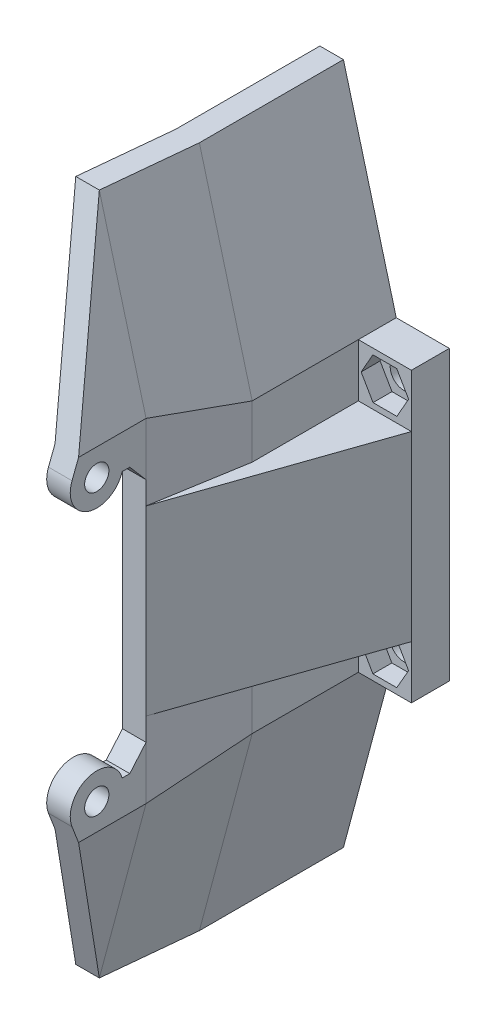
SolidWorks part; units mm, degrees
note: The reader was unsure of these and kept them because the rebuilt part matched: shared geometry of "Esquisse3<4>".
ref_plane "Plan de face" through (0, 0, 0) normal (0, 0, 1) x (1, 0, 0)
ref_plane "Plan de dessus" through (0, 0, 0) normal (0, 1, 0) x (1, 0, 0)
ref_plane "Plan de droite" through (0, 0, 0) normal (1, 0, 0) x (0, 0, -1)
sketch "Esquisse1" plane through (0, 0, 0) normal (0, 0, 1) x (1, 0, 0)
  line L1 (-10.1058, -19) -> (-10.1058, 19)
  line L2 (-10.1058, 19) -> (-17.0725, 45)
  line L3 (-17.0725, 45) -> (-13.9667, 45)
  line L4 (-13.9667, 45) -> (-7, 19)
  line L5 (-7, -19) -> (-13.9667, -45)
  line L6 (-7, 19) -> (0, 19)
  line L7 (0, 19) -> (0, -19)
  line L8 (-7, -19) -> (0, -19)
  line L11 (-17.0725, -45) -> (-13.9667, -45)
  line L12 (-10.1058, -19) -> (-17.0725, -45)
  point P10 (0, 0)
  dimension "D1" = 3
  dimension "D2" = 3
  dimension "D3" = 165
  dimension "D4" = 7
  dimension "D5" = 38
  dimension "D6" = 165
  dimension "D7" = 90
extrude "Boss.-Extru.1" add sketch "Esquisse1" along normal blind 5
sketch "Esquisse2" plane through (0, 0, 5) normal (0, 0, 1) x (1, 0, 0)
  line L8 (-17.0725, 45) -> (-10.1058, 19)
  line L9 (-17.0725, 45) -> (-10.1058, 19)
  line L10 (-10.1058, 19) -> (-10.1058, -19)
  line L11 (-10.1058, 19) -> (-10.1058, -19)
  line L12 (-7, 19) -> (-7, -19)
  line L13 (-10.1058, -19) -> (-17.0725, -45)
  line L14 (-10.1058, -19) -> (-17.0725, -45)
  line L15 (-17.0725, -45) -> (-13.9667, -45)
  line L16 (-17.0725, -45) -> (-13.9667, -45)
  line L17 (-13.9667, -45) -> (-7, -19)
  line L18 (-13.9667, -45) -> (-7, -19)
  line L19 (-7, 19) -> (-13.9667, 45)
  line L20 (-7, -19) -> (0, -19)
  line L21 (0, -19) -> (0, 19)
  line L22 (0, 19) -> (-7, 19)
  line L23 (-7, 19) -> (-13.9667, 45)
  line L30 (-13.9667, 45) -> (-17.0725, 45)
  line L31 (-13.9667, 45) -> (-17.0725, 45)
  dimension "D1" = 0
extrude "Boss.-Extru.2" add sketch "Esquisse2" along normal blind 14
ref_plane "Plan2" through (0, 0, 31) normal (0, 0, 1) x (1, 0, 0)
sketch "Esquisse3" plane through (0, 0, 31) normal (0, 0, 1) x (1, 0, 0)
  line L0 (-18.2687, 45) -> (-15.1628, 45)
  line L1 (-15.1628, 45) -> (-9, 22)
  line L3 (-9, 22) -> (-9, -22)
  line L4 (-18.2687, 45) -> (-12.1058, 22)
  line L5 (-12.1058, -22) -> (-12.1058, 22)
  line L7 (-18.2687, -45) -> (-12.1058, -22)
  line L8 (-15.1628, -45) -> (-9, -22)
  line L9 (-18.2687, -45) -> (-15.1628, -45)
  line L19 (-7, -19) -> (-7, 19) construction
  point P5 (-9, 0)
  dimension "D2" = 2
  dimension "D3" = 44
  dimension "D4" = 44
  dimension "D5" = 3
  dimension "D13" = 3
  dimension "D14" = 165
  dimension "D15" = 165
  dimension "D16" = 90
sketch "Esquisse4" plane through (0, 0, 19) normal (0, 0, 1) x (1, 0, 0)
  line L8 (-13.9667, 45) -> (-17.0725, 45)
  line L9 (-17.0725, 45) -> (-10.1058, 19)
  line L10 (-10.1058, 19) -> (-10.1058, -19)
  line L11 (-10.1058, -19) -> (-17.0725, -45)
  line L12 (-17.0725, -45) -> (-13.9667, -45)
  line L13 (-13.9667, -45) -> (-7, -19)
  line L14 (-7, -19) -> (-7, 19)
  line L15 (-13.9667, -45) -> (-7, -19)
  line L16 (-13.9667, 45) -> (-17.0725, 45)
  line L17 (-17.0725, 45) -> (-10.1058, 19)
  line L18 (-10.1058, 19) -> (-10.1058, -19)
  line L19 (-10.1058, -19) -> (-17.0725, -45)
  line L20 (-17.0725, -45) -> (-13.9667, -45)
  line L21 (-7, 19) -> (-13.9667, 45)
  line L22 (-7, -19) -> (-7, 19)
  line L23 (-7, 19) -> (-13.9667, 45)
  dimension "D1" = 0
loft "Lissage1" add profiles "Esquisse4", "Esquisse3"
sketch "Esquisse5" plane through (0, 0, 5) normal (0, 0, 1) x (1, 0, 0)
  line L1 (-3.5, 15.5) -> (-3.5, -15.5) construction
  line L2 (0, -19) -> (0, 19) construction
  line L3 (-7, 0) -> (0, 0) construction
  line L4 (-7, -19) -> (-7, 19) construction
  line L5 (0, 19) -> (-7, 19) construction
  circle A0 centre (-3.5, -15.5) radius 1.8
  circle A1 centre (-3.5, 15.5) radius 1.8
  dimension "D1" = 3.6
  dimension "D4" = 15.5
  dimension "D2" = 3.5
  dimension "D3" = 3.5
extrude "Enlèv. mat.-Extru.1" cut sketch "Esquisse5" against normal through all
sketch "Esquisse6" plane through (0, 0, 31) normal (0, 0, 1) x (1, 0, 0)
  line L0 (-18.2687, 45) -> (-12.1058, 22) construction
  line L1 (-9, 45) -> (-18.2687, 45)
  line L2 (-9, 45) -> (-9, -45)
  line L3 (-9, 22) -> (-15.1628, 45) construction
  line L4 (-18.2687, 45) -> (-12.1058, 22)
  line L5 (9.4027, 22) -> (-26.5203, 22) construction
  line L6 (11.0972, 0) -> (-26.5203, 0) construction
  line L7 (-12.1058, 22) -> (-12.1058, -22)
  line L8 (-12.1058, 22) -> (-12.1058, -22) construction
  line L9 (-18.2687, -45) -> (-12.1058, -22)
  line L10 (-9, -45) -> (-18.2687, -45)
  line L11 (-15.1628, 45) -> (-18.2687, 45) construction
  point P2 (-9, -22)
  point P8 (-9, 22)
  point P19 (-12.1058, 0)
  point P21 (-9, 0)
  dimension "D1" = 22
extrude "Boss.-Extru.3" add sketch "Esquisse6" along normal blind 15
sketch "Esquisse7" plane through (-9, 0, 0) normal (-1, 0, 0) x (0, 0, 1)
  line L0 (66.6395, 0) -> (-18.721, 0) construction
  line L1 (31, 22) -> (31, 45) construction
  line L2 (34.1459, 17.5) -> (33.1459, 17.5)
  line L3 (33.1459, 17.5) -> (31, 15)
  line L5 (31, 22) -> (31, -22) construction
  line L6 (37.5, 15) -> (27.5292, 15) construction
  line L8 (40.7642, 19.7629) -> (31, 45)
  line L10 (31, 15) -> (31, 45)
  line L11 (31, -15) -> (31, -45)
  line L12 (40.7642, -19.7629) -> (31, -45)
  line L13 (33.1459, -17.5) -> (31, -15)
  line L14 (34.1459, -17.5) -> (33.1459, -17.5)
  line L15 (31, 22) -> (31, -22) construction
  circle A0 centre (37.5, 18.5) radius 1.6
  circle A1 centre (37.5, 18.5) radius 3.5
  circle A2 centre (37.5, -18.5) radius 3.5
  circle A3 centre (37.5, -18.5) radius 1.6
  dimension "D1" = 3.2
  dimension "D2" = 7
  dimension "D3" = 18.5
  dimension "D4" = 6.5
  dimension "D5" = 1
  dimension "D6" = 1
extrude "Enlèv. mat.-Extru.2" cut sketch "Esquisse7" along normal through all
extrude "Enlèv. mat.-Extru.5" cut sketch "Esquisse3<4>" along normal through all flip side to cut
sketch "Esquisse3<4>" plane through (0, 0, 31) normal (0, 0, 1) x (1, 0, 0) same geometry as "Esquisse3"
sketch "Esquisse9" plane through (0, 0, 0) normal (0, -1, 0) x (-1, 0, 0)
  line L0 (0, -5) -> (9, -31)
rib "Nervure2" sketch "Esquisse9" sketch "Esquisse9" thickness 24 extrusion direction parallel to sketch draft on no parameters "D1"=24
sketch "Esquisse10" plane through (0, 0, 5) normal (0, 0, 1) x (1, 0, 0)
  line L0 (-5.0799, 18.2252) -> (-1.9395, 18.2252)
  line L1 (-1.9395, 18.2252) -> (-0.3694, 15.5056)
  line L2 (-0.3694, 15.5056) -> (-1.9201, 12.7748)
  line L3 (-1.9201, 12.7748) -> (-5.0605, 12.7748)
  line L4 (-5.0605, 12.7748) -> (-6.6306, 15.4944)
  line L5 (-6.6306, 15.4944) -> (-5.0799, 18.2252)
  line L6 (-5.0799, 18.2252) -> (-1.9201, 12.7748) construction
  line L7 (0, 0) -> (-9, 0) construction
  line L8 (-9, -12) -> (-9, 12) construction
  line L9 (-5.0799, -18.2252) -> (-1.9201, -12.7748) construction
  line L10 (-6.6306, -15.4944) -> (-5.0799, -18.2252)
  line L11 (-5.0605, -12.7748) -> (-6.6306, -15.4944)
  line L12 (-1.9201, -12.7748) -> (-5.0605, -12.7748)
  line L13 (-0.3694, -15.5056) -> (-1.9201, -12.7748)
  line L14 (-1.9395, -18.2252) -> (-0.3694, -15.5056)
  line L15 (-5.0799, -18.2252) -> (-1.9395, -18.2252)
  point P0 (-3.5, 15.5)
  point P6 (-3.5, 15.5)
  point P20 (-3.5, -15.5)
  dimension "D1" = 120
  dimension "D2" = 6.3
extrude "Enlèv. mat.-Extru.6" cut sketch "Esquisse10" against normal blind 2.5
